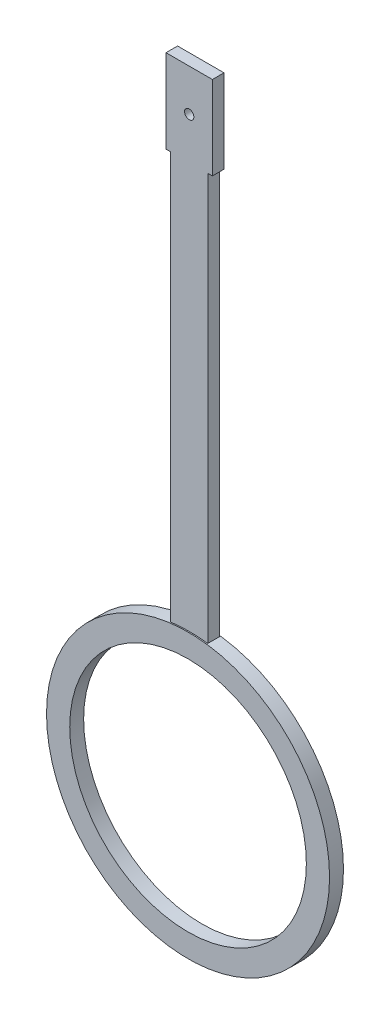
SolidWorks part; units mm, degrees
material "Gray Cast Iron"
ref_plane "Front Plane" through (0, 0, 0) normal (0, 0, 1) x (1, 0, 0)
ref_plane "Top Plane" through (0, 0, 0) normal (0, 1, 0) x (1, 0, 0)
ref_plane "Right Plane" through (0, 0, 0) normal (1, 0, 0) x (0, 0, -1)
sketch "Sketch1" plane through (0, 0, 0) normal (0, 0, 1) x (1, 0, 0)
  circle A0 centre (0, 0) radius 30.5
  dimension "D1" = 61
extrude "Boss-Extrude1" add sketch "Sketch1" along normal mid plane 3
sketch "Sketch2" plane through (0, 0, 0) normal (0, 0, 1) x (1, 0, 0)
  line L0 (-4, 25) -> (4, 25)
  line L1 (4, 25) -> (4, 118)
  line L2 (4, 118) -> (-4, 118)
  line L3 (-4, 118) -> (-4, 25)
  dimension "D1" = 8
  dimension "D2" = 93
  dimension "D3" = 4
  dimension "D4" = 25
extrude "Boss-Extrude2" add sketch "Sketch2" along normal mid plane 2.5
sketch "Sketch3" plane through (0, 0, 0) normal (0, 0, 1) x (1, 0, 0)
  line L0 (-5, 118) -> (5, 118)
  line L1 (5, 118) -> (5, 136)
  line L2 (5, 136) -> (-5, 136)
  line L3 (-5, 136) -> (-5, 118)
  dimension "D1" = 10
  dimension "D2" = 18
  dimension "D3" = 5
  dimension "D4" = 118
extrude "Boss-Extrude3" add sketch "Sketch3" along normal mid plane 2.5
sketch "Sketch4" plane through (0, 0, 0) normal (0, 0, 1) x (1, 0, 0)
  circle A0 centre (0, 0) radius 25.5
  dimension "D1" = 51
extrude "Cut-Extrude1" cut sketch "Sketch4" against normal mid plane 20
sketch "Sketch5" plane through (0, 0, 0) normal (0, 0, 1) x (1, 0, 0)
  circle A0 centre (0, 127) radius 1
  dimension "D2" = 2
  dimension "D1" = 127
extrude "Cut-Extrude2" cut sketch "Sketch5" against normal mid plane 20
ref_axis "Axis1" through (0, 0, 1.65) along (0, 0, -1)
ref_plane "Plane1" through (0, 127, 0) normal (0, 1, 0) x (1, 0, 0)
ref_axis "Axis2" through (0, 127, 1.65) along (0, 0, -1)
